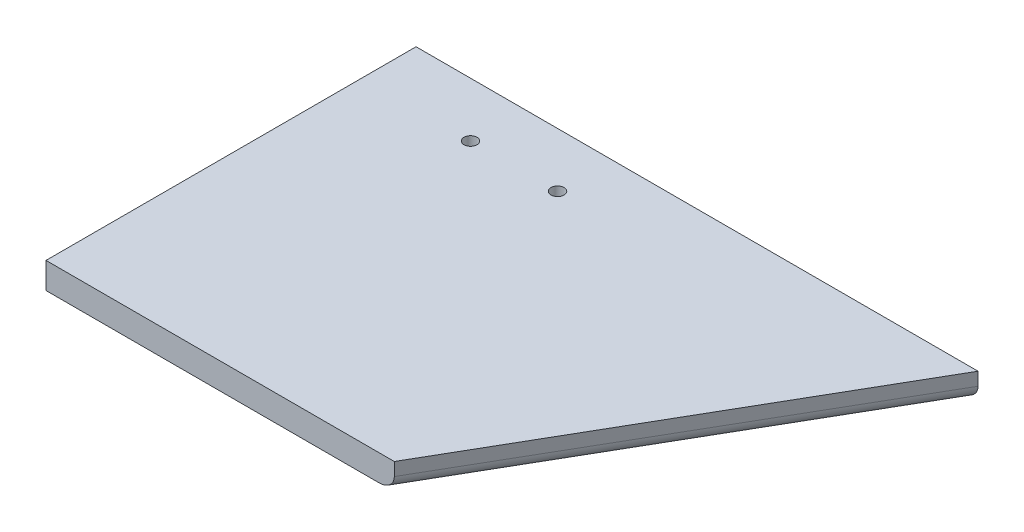
SolidWorks part; units mm, degrees
ref_plane "Front" through (0, 0, 0) normal (0, 0, 1) x (1, 0, 0)
ref_plane "Top" through (0, 0, 0) normal (0, 1, 0) x (1, 0, 0)
ref_plane "Right" through (0, 0, 0) normal (1, 0, 0) x (0, 0, -1)
sketch "Sketch1" plane through (0, 0, 0) normal (0, 1, 0) x (1, 0, 0)
  line L0 (0, 0) -> (49.0748, 85)
  line L1 (0, 0) -> (-80, 0)
  line L3 (0, 85) -> (-80, 85)
  line L4 (-80, 0) -> (-80, 85)
  line L5 (49.0748, 85) -> (0, 85)
  dimension "D1" = 80
  dimension "D2" = 85
  dimension "D3" = 120
extrude "Boss-Extrude1" add sketch "Sketch1" along normal blind 6
fillet "Fillet1" radius 3 1 edges at (24.5374, 0, -42.5)
sketch "Sketch2" plane through (0, 6, 0) normal (0, 1, 0) x (1, 0, 0)
  line L0 (-80, 85) -> (-80, 0) construction
  line L1 (49.0748, 85) -> (-80, 85) construction
  circle A0 centre (-55, 72.5) radius 1.5
  circle A1 centre (-35, 72.5) radius 1.5
  dimension "D1" = 3
  dimension "D2" = 20
  dimension "D3" = 25
  dimension "D4" = 12.5
extrude "Cut-Extrude1" cut sketch "Sketch2" against normal through all
